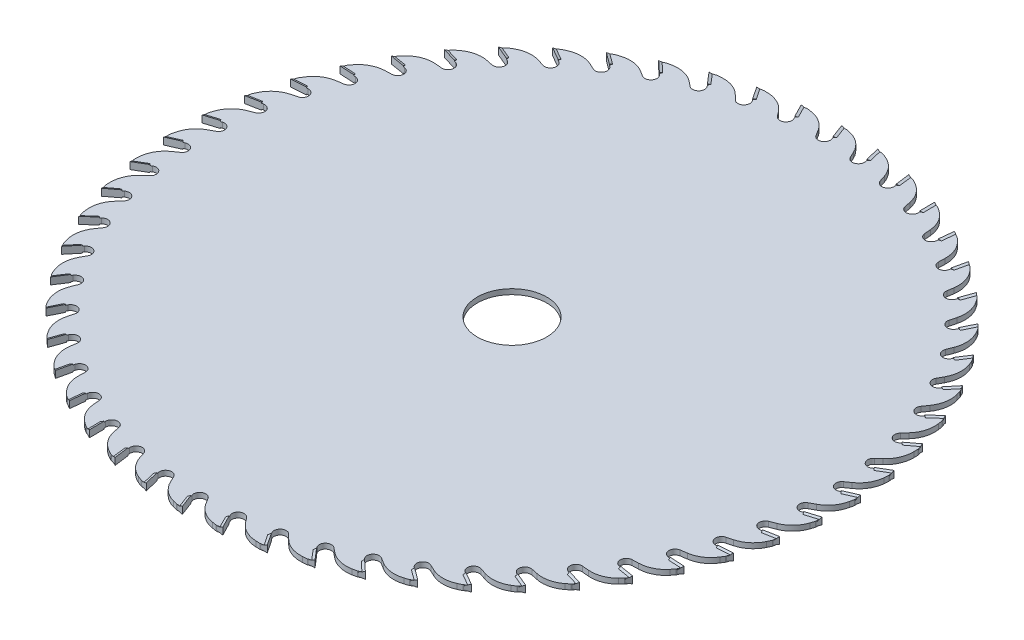
SolidWorks part; units mm, degrees
material "AISI Type A2 Tool Steel"
ref_plane "Front Plane" through (0, 0, 0) normal (0, 0, 1) x (1, 0, 0)
ref_plane "Top Plane" through (0, 0, 0) normal (0, 1, 0) x (1, 0, 0)
ref_plane "Right Plane" through (0, 0, 0) normal (1, 0, 0) x (0, 0, -1)
sketch "Sketch1" plane through (0, 0, 0) normal (0, 1, 0) x (1, 0, 0)
  line L0 (1.6393, 90.6125) -> (0, 95)
  line L1 (-1.4909, 89.0836) -> (-2.4449, 90.6357)
  line L2 (-8.0715, 94.3576) -> (-9.3059, 94.5431)
  line L3 (12.1477, 89.8095) -> (11.0288, 94.3576)
  line L4 (8.8612, 88.6543) -> (8.0938, 90.3067)
  line L5 (2.9373, 94.6567) -> (1.7328, 94.9842)
  line L6 (22.4918, 87.792) -> (21.9085, 92.4393)
  line L7 (19.0934, 87.0262) -> (18.523, 88.7564)
  line L8 (13.9064, 93.6756) -> (12.7481, 94.1408)
  line L9 (32.5317, 84.5872) -> (32.4919, 89.2708)
  line L10 (29.0674, 84.2211) -> (28.7018, 86.0059)
  line L11 (24.6874, 91.4278) -> (23.5909, 92.0243)
  line L12 (42.1318, 80.2386) -> (42.6359, 84.8951)
  line L13 (38.6484, 80.2771) -> (38.4924, 82.0923)
  line L14 (35.1346, 87.9436) -> (34.1148, 88.6633)
  line L15 (51.162, 74.8048) -> (52.2034, 79.3713)
  line L16 (47.7066, 75.2475) -> (47.7624, 77.0685)
  line L17 (45.1067, 83.27) -> (44.1773, 84.1033)
  line L18 (59.5004, 68.3595) -> (61.0648, 72.7742)
  line L19 (56.1198, 69.2003) -> (56.3866, 71.0025)
  line L20 (54.4687, 77.4704) -> (53.6424, 78.406)
  line L21 (67.0341, 60.9897) -> (69.1005, 65.193)
  line L22 (63.774, 62.2173) -> (64.2482, 63.9764)
  line L23 (63.0942, 70.6232) -> (62.382, 71.6483)
  line L24 (73.6613, 52.7951) -> (76.2017, 56.7301)
  line L25 (70.5657, 54.3929) -> (71.241, 56.085)
  line L26 (70.8664, 62.8208) -> (70.2781, 63.9217)
  line L27 (79.2924, 43.8866) -> (82.2724, 47.5)
  line L28 (76.4032, 45.8329) -> (77.2704, 47.4352)
  line L29 (77.6803, 54.169) -> (77.2238, 55.3307)
  line L30 (83.8512, 34.3845) -> (87.2305, 37.6276)
  line L31 (81.2075, 36.6532) -> (82.2548, 38.1439)
  line L32 (83.4437, 44.7846) -> (83.1251, 45.9915)
  line L33 (87.276, 24.4175) -> (91.009, 27.2463)
  line L34 (84.9136, 26.9777) -> (86.1268, 28.3368)
  line L35 (88.0787, 34.7945) -> (87.9023, 36.0303)
  line L36 (89.5206, 14.1203) -> (93.5567, 16.4966)
  line L37 (87.4713, 16.9374) -> (88.8342, 18.1465)
  line L38 (91.5225, 24.3339) -> (91.4908, 25.5818)
  line L39 (90.5545, 3.6321) -> (94.8393, 5.5238)
  line L40 (88.8462, 6.6681) -> (90.3402, 7.7108)
  line L41 (93.7287, 13.5443) -> (93.8421, 14.7874)
  line L42 (90.3639, -6.9052) -> (94.8393, -5.5238)
  line L43 (89.0196, -3.6914) -> (90.6245, -2.8292)
  line L44 (94.6673, 2.5715) -> (94.9242, 3.793)
  line L45 (88.9512, -17.3491) -> (93.5567, -16.4966)
  line L46 (87.9891, -14.001) -> (89.6833, -13.331)
  line L47 (94.3257, -8.4361) -> (94.7227, -7.2527)
  line L48 (86.3357, -27.5584) -> (91.009, -27.2463)
  line L49 (85.7687, -24.1212) -> (87.5293, -23.6524)
  line L50 (92.7086, -19.3296) -> (93.2403, -18.2003)
  line L51 (82.5526, -37.395) -> (87.2305, -37.6276)
  line L52 (82.3885, -33.9153) -> (84.1915, -33.654)
  line L53 (89.8377, -29.9617) -> (90.4969, -28.9018)
  line L54 (77.6531, -46.7259) -> (82.2724, -47.5)
  line L55 (77.8941, -43.2507) -> (79.7153, -43.2005)
  line L56 (85.7519, -40.1886) -> (86.5297, -39.2124)
  line L57 (71.7035, -55.425) -> (76.2017, -56.7301)
  line L58 (72.3463, -52.0012) -> (74.161, -52.1628)
  line L59 (80.5064, -49.8721) -> (81.3923, -48.9927)
  line L60 (64.7842, -63.3745) -> (69.1005, -65.193)
  line L61 (65.8202, -60.0485) -> (67.6038, -60.4196)
  line L62 (74.1723, -58.8811) -> (75.1543, -58.1105)
  line L63 (56.9888, -70.4669) -> (61.0648, -72.7742)
  line L64 (58.4039, -67.2837) -> (60.1324, -67.8594)
  line L65 (66.8351, -67.0938) -> (67.8999, -66.4425)
  line L66 (48.4228, -76.6065) -> (52.2034, -79.3713)
  line L67 (50.1978, -73.609) -> (51.8478, -74.3815)
  line L68 (58.594, -74.3993) -> (59.7273, -73.8759)
  line L69 (39.2019, -81.71) -> (42.6359, -84.8951)
  line L70 (41.3129, -78.9389) -> (42.8621, -79.8978)
  line L71 (49.5606, -80.6985) -> (50.747, -80.3103)
  line L72 (29.4509, -85.7086) -> (32.4919, -89.2708)
  line L73 (31.8693, -83.2013) -> (33.2967, -84.3335)
  line L74 (39.857, -85.9065) -> (41.0804, -85.6586)
  line L75 (19.3016, -88.5481) -> (21.9085, -92.4393)
  line L76 (21.9948, -86.3385) -> (23.281, -87.6288)
  line L77 (29.6143, -89.9528) -> (30.8582, -89.8486)
  line L78 (8.8912, -90.1901) -> (11.0288, -94.3576)
  line L79 (11.8228, -88.3082) -> (12.9505, -89.739)
  line L80 (18.9712, -92.7826) -> (20.2188, -92.8235)
  line L81 (-1.6393, -90.6125) -> (0, -95)
  line L82 (1.4909, -89.0836) -> (2.4449, -90.6357)
  line L83 (8.0715, -94.3576) -> (9.3059, -94.5431)
  line L84 (-12.1477, -89.8095) -> (-11.0288, -94.3576)
  line L85 (-8.8612, -88.6543) -> (-8.0938, -90.3067)
  line L86 (-2.9373, -94.6567) -> (-1.7328, -94.9842)
  line L87 (-22.4918, -87.792) -> (-21.9085, -92.4393)
  line L88 (-19.0934, -87.0262) -> (-18.523, -88.7564)
  line L89 (-13.9064, -93.6756) -> (-12.7481, -94.1408)
  line L90 (-32.5317, -84.5872) -> (-32.4919, -89.2708)
  line L91 (-29.0674, -84.2211) -> (-28.7018, -86.0059)
  line L92 (-24.6874, -91.4278) -> (-23.5909, -92.0243)
  line L93 (-42.1318, -80.2386) -> (-42.6359, -84.8951)
  line L94 (-38.6484, -80.2771) -> (-38.4924, -82.0923)
  line L95 (-35.1346, -87.9436) -> (-34.1148, -88.6633)
  line L96 (-51.162, -74.8048) -> (-52.2034, -79.3713)
  line L97 (-47.7066, -75.2475) -> (-47.7624, -77.0685)
  line L98 (-45.1067, -83.27) -> (-44.1773, -84.1033)
  line L99 (-59.5004, -68.3595) -> (-61.0648, -72.7742)
  line L100 (-56.1198, -69.2003) -> (-56.3866, -71.0025)
  line L101 (-54.4687, -77.4704) -> (-53.6424, -78.406)
  line L102 (-67.0341, -60.9897) -> (-69.1005, -65.193)
  line L103 (-63.774, -62.2173) -> (-64.2482, -63.9764)
  line L104 (-63.0942, -70.6232) -> (-62.382, -71.6483)
  line L105 (-73.6613, -52.7951) -> (-76.2017, -56.7301)
  line L106 (-70.5657, -54.3929) -> (-71.241, -56.085)
  line L107 (-70.8664, -62.8208) -> (-70.2781, -63.9217)
  line L108 (-79.2924, -43.8866) -> (-82.2724, -47.5)
  line L109 (-76.4032, -45.8329) -> (-77.2704, -47.4352)
  line L110 (-77.6803, -54.169) -> (-77.2238, -55.3307)
  line L111 (-83.8512, -34.3845) -> (-87.2305, -37.6276)
  line L112 (-81.2075, -36.6532) -> (-82.2548, -38.1439)
  line L113 (-83.4437, -44.7846) -> (-83.1251, -45.9915)
  line L114 (-87.276, -24.4175) -> (-91.009, -27.2463)
  line L115 (-84.9136, -26.9777) -> (-86.1268, -28.3368)
  line L116 (-88.0787, -34.7945) -> (-87.9023, -36.0303)
  line L117 (-89.5206, -14.1203) -> (-93.5567, -16.4966)
  line L118 (-87.4713, -16.9374) -> (-88.8342, -18.1465)
  line L119 (-91.5225, -24.3339) -> (-91.4908, -25.5818)
  line L120 (-90.5545, -3.6321) -> (-94.8393, -5.5238)
  line L121 (-88.8462, -6.6681) -> (-90.3402, -7.7108)
  line L122 (-93.7287, -13.5443) -> (-93.8421, -14.7874)
  line L123 (-90.3639, 6.9052) -> (-94.8393, 5.5238)
  line L124 (-89.0196, 3.6914) -> (-90.6245, 2.8292)
  line L125 (-94.6673, -2.5715) -> (-94.9242, -3.793)
  line L126 (-88.9512, 17.3491) -> (-93.5567, 16.4966)
  line L127 (-87.9891, 14.001) -> (-89.6833, 13.331)
  line L128 (-94.3257, 8.4361) -> (-94.7227, 7.2527)
  line L129 (-86.3357, 27.5584) -> (-91.009, 27.2463)
  line L130 (-85.7687, 24.1212) -> (-87.5293, 23.6524)
  line L131 (-92.7086, 19.3296) -> (-93.2403, 18.2003)
  line L132 (-82.5526, 37.395) -> (-87.2305, 37.6276)
  line L133 (-82.3885, 33.9153) -> (-84.1915, 33.654)
  line L134 (-89.8377, 29.9617) -> (-90.4969, 28.9018)
  line L135 (-77.6531, 46.7259) -> (-82.2724, 47.5)
  line L136 (-77.8941, 43.2507) -> (-79.7153, 43.2005)
  line L137 (-85.7519, 40.1886) -> (-86.5297, 39.2124)
  line L138 (-71.7035, 55.425) -> (-76.2017, 56.7301)
  line L139 (-72.3463, 52.0012) -> (-74.161, 52.1628)
  line L140 (-80.5064, 49.8721) -> (-81.3923, 48.9927)
  line L141 (-64.7842, 63.3745) -> (-69.1005, 65.193)
  line L142 (-65.8202, 60.0485) -> (-67.6038, 60.4196)
  line L143 (-74.1723, 58.8811) -> (-75.1543, 58.1105)
  line L144 (-56.9888, 70.4669) -> (-61.0648, 72.7742)
  line L145 (-58.4039, 67.2837) -> (-60.1324, 67.8594)
  line L146 (-66.8351, 67.0938) -> (-67.8999, 66.4425)
  line L147 (-48.4228, 76.6065) -> (-52.2034, 79.3713)
  line L148 (-50.1978, 73.609) -> (-51.8478, 74.3815)
  line L149 (-58.594, 74.3993) -> (-59.7273, 73.8759)
  line L150 (-39.2019, 81.71) -> (-42.6359, 84.8951)
  line L151 (-41.3129, 78.9389) -> (-42.8621, 79.8978)
  line L152 (-49.5606, 80.6985) -> (-50.747, 80.3103)
  line L153 (-29.4509, 85.7086) -> (-32.4919, 89.2708)
  line L154 (-31.8693, 83.2013) -> (-33.2967, 84.3335)
  line L155 (-39.857, 85.9065) -> (-41.0804, 85.6586)
  line L156 (-19.3016, 88.5481) -> (-21.9085, 92.4393)
  line L157 (-21.9948, 86.3385) -> (-23.281, 87.6288)
  line L158 (-29.6143, 89.9528) -> (-30.8582, 89.8486)
  line L159 (-8.8912, 90.1901) -> (-11.0288, 94.3576)
  line L160 (-11.8228, 88.3082) -> (-12.9505, 89.739)
  line L161 (-18.9712, 92.7826) -> (-20.2188, 92.8235)
  circle A0 centre (0, 0) radius 10
  circle A1 centre (0, 0) radius 95
  circle A2 centre (0, 90) radius 1.75
  arc A3 (-2.4449, 90.6357) -> (-8.0715, 94.3576) centre (-9.2603, 86.4464) ccw
  circle A4 centre (10.4484, 89.3915) radius 1.75
  arc A5 (8.0938, 90.3067) -> (2.9373, 94.6567) centre (0.8381, 86.937) ccw
  circle A6 centre (20.7554, 87.574) radius 1.75
  arc A7 (18.523, 88.7564) -> (13.9064, 93.6756) centre (10.9252, 86.2518) ccw
  circle A8 centre (30.7818, 84.5723) radius 1.75
  arc A9 (28.7018, 86.0059) -> (24.6874, 91.4278) centre (20.8645, 84.4003) ccw
  circle A10 centre (40.3919, 80.4269) radius 1.75
  arc A11 (38.4924, 82.0923) -> (35.1346, 87.9436) centre (30.5217, 81.4074) ccw
  circle A12 centre (49.4558, 75.1939) radius 1.75
  arc A13 (47.7624, 77.0685) -> (45.1067, 83.27) centre (39.7662, 77.3136) ccw
  circle A14 centre (57.8509, 68.944) radius 1.75
  arc A15 (56.3866, 71.0025) -> (54.4687, 77.4704) centre (48.4729, 72.1742) ccw
  circle A16 centre (65.4636, 61.7617) radius 1.75
  arc A17 (64.2482, 63.9764) -> (63.0942, 70.6232) centre (56.524, 66.0589) ccw
  circle A18 centre (72.1911, 53.7443) radius 1.75
  arc A19 (71.241, 56.085) -> (70.8664, 62.8208) centre (63.8108, 59.0502) ccw
  circle A20 centre (77.9423, 45) radius 1.75
  arc A21 (77.2704, 47.4352) -> (77.6803, 54.169) centre (70.2346, 51.2429) ccw
  circle A22 centre (82.6394, 35.6472) radius 1.75
  arc A23 (82.2548, 38.1439) -> (83.4437, 44.7846) centre (75.7087, 42.7427) ccw
  circle A24 centre (86.2191, 25.8123) radius 1.75
  arc A25 (86.1268, 28.3368) -> (88.0787, 34.7945) centre (80.1589, 33.6644) ccw
  circle A26 centre (88.6327, 15.6283) radius 1.75
  arc A27 (88.8342, 18.1465) -> (91.5225, 24.3339) centre (83.5251, 24.1309) ccw
  circle A28 centre (89.8477, 5.233) radius 1.75
  arc A29 (90.3402, 7.7108) -> (93.7287, 13.5443) centre (85.7617, 14.2711) ccw
  circle A30 centre (89.8477, -5.233) radius 1.75
  arc A31 (90.6245, -2.8292) -> (94.6673, 2.5715) centre (86.8386, 4.2183) ccw
  circle A32 centre (88.6327, -15.6283) radius 1.75
  arc A33 (89.6833, -13.331) -> (94.3257, -8.4361) centre (86.7412, -5.8916) ccw
  circle A34 centre (86.2191, -25.8123) radius 1.75
  arc A35 (87.5293, -23.6524) -> (92.7086, -19.3296) centre (85.4707, -15.9218) ccw
  circle A36 centre (82.6394, -35.6472) radius 1.75
  arc A37 (84.1915, -33.654) -> (89.8377, -29.9617) centre (83.0443, -25.7367) ccw
  circle A38 centre (77.9423, -45) radius 1.75
  arc A39 (79.7153, -43.2005) -> (85.7519, -40.1886) centre (79.495, -35.2035) ccw
  circle A40 centre (72.1911, -53.7443) radius 1.75
  arc A41 (74.161, -52.1628) -> (80.5064, -49.8721) centre (74.8706, -44.1943) ccw
  circle A42 centre (65.4636, -61.7617) radius 1.75
  arc A43 (67.6038, -60.4196) -> (74.1723, -58.8811) centre (69.2337, -52.5874) ccw
  circle A44 centre (57.8509, -68.944) radius 1.75
  arc A45 (60.1324, -67.8594) -> (66.8351, -67.0938) centre (62.6605, -60.2694) ccw
  circle A46 centre (49.4558, -75.1939) radius 1.75
  arc A47 (51.8478, -74.3815) -> (58.594, -74.3993) centre (55.24, -67.1363) ccw
  circle A48 centre (40.3919, -80.4269) radius 1.75
  arc A49 (42.8621, -79.8978) -> (49.5606, -80.6985) centre (47.0724, -73.0953) ccw
  circle A50 centre (30.7818, -84.5723) radius 1.75
  arc A51 (33.2967, -84.3335) -> (39.857, -85.9065) centre (38.2683, -78.0659) ccw
  circle A52 centre (20.7554, -87.574) radius 1.75
  arc A53 (23.281, -87.6288) -> (29.6143, -89.9528) centre (28.9467, -81.9807) ccw
  circle A54 centre (10.4484, -89.3915) radius 1.75
  arc A55 (12.9505, -89.739) -> (18.9712, -92.7826) centre (19.2335, -84.7869) ccw
  circle A56 centre (0, -90) radius 1.75
  arc A57 (2.4449, -90.6357) -> (8.0715, -94.3576) centre (9.2603, -86.4464) ccw
  circle A58 centre (-10.4484, -89.3915) radius 1.75
  arc A59 (-8.0938, -90.3067) -> (-2.9373, -94.6567) centre (-0.8381, -86.937) ccw
  circle A60 centre (-20.7554, -87.574) radius 1.75
  arc A61 (-18.523, -88.7564) -> (-13.9064, -93.6756) centre (-10.9252, -86.2518) ccw
  circle A62 centre (-30.7818, -84.5723) radius 1.75
  arc A63 (-28.7018, -86.0059) -> (-24.6874, -91.4278) centre (-20.8645, -84.4003) ccw
  circle A64 centre (-40.3919, -80.4269) radius 1.75
  arc A65 (-38.4924, -82.0923) -> (-35.1346, -87.9436) centre (-30.5217, -81.4074) ccw
  circle A66 centre (-49.4558, -75.1939) radius 1.75
  arc A67 (-47.7624, -77.0685) -> (-45.1067, -83.27) centre (-39.7662, -77.3136) ccw
  circle A68 centre (-57.8509, -68.944) radius 1.75
  arc A69 (-56.3866, -71.0025) -> (-54.4687, -77.4704) centre (-48.4729, -72.1742) ccw
  circle A70 centre (-65.4636, -61.7617) radius 1.75
  arc A71 (-64.2482, -63.9764) -> (-63.0942, -70.6232) centre (-56.524, -66.0589) ccw
  circle A72 centre (-72.1911, -53.7443) radius 1.75
  arc A73 (-71.241, -56.085) -> (-70.8664, -62.8208) centre (-63.8108, -59.0502) ccw
  circle A74 centre (-77.9423, -45) radius 1.75
  arc A75 (-77.2704, -47.4352) -> (-77.6803, -54.169) centre (-70.2346, -51.2429) ccw
  circle A76 centre (-82.6394, -35.6472) radius 1.75
  arc A77 (-82.2548, -38.1439) -> (-83.4437, -44.7846) centre (-75.7087, -42.7427) ccw
  circle A78 centre (-86.2191, -25.8123) radius 1.75
  arc A79 (-86.1268, -28.3368) -> (-88.0787, -34.7945) centre (-80.1589, -33.6644) ccw
  circle A80 centre (-88.6327, -15.6283) radius 1.75
  arc A81 (-88.8342, -18.1465) -> (-91.5225, -24.3339) centre (-83.5251, -24.1309) ccw
  circle A82 centre (-89.8477, -5.233) radius 1.75
  arc A83 (-90.3402, -7.7108) -> (-93.7287, -13.5443) centre (-85.7617, -14.2711) ccw
  circle A84 centre (-89.8477, 5.233) radius 1.75
  arc A85 (-90.6245, 2.8292) -> (-94.6673, -2.5715) centre (-86.8386, -4.2183) ccw
  circle A86 centre (-88.6327, 15.6283) radius 1.75
  arc A87 (-89.6833, 13.331) -> (-94.3257, 8.4361) centre (-86.7412, 5.8916) ccw
  circle A88 centre (-86.2191, 25.8123) radius 1.75
  arc A89 (-87.5293, 23.6524) -> (-92.7086, 19.3296) centre (-85.4707, 15.9218) ccw
  circle A90 centre (-82.6394, 35.6472) radius 1.75
  arc A91 (-84.1915, 33.654) -> (-89.8377, 29.9617) centre (-83.0443, 25.7367) ccw
  circle A92 centre (-77.9423, 45) radius 1.75
  arc A93 (-79.7153, 43.2005) -> (-85.7519, 40.1886) centre (-79.495, 35.2035) ccw
  circle A94 centre (-72.1911, 53.7443) radius 1.75
  arc A95 (-74.161, 52.1628) -> (-80.5064, 49.8721) centre (-74.8706, 44.1943) ccw
  circle A96 centre (-65.4636, 61.7617) radius 1.75
  arc A97 (-67.6038, 60.4196) -> (-74.1723, 58.8811) centre (-69.2337, 52.5874) ccw
  circle A98 centre (-57.8509, 68.944) radius 1.75
  arc A99 (-60.1324, 67.8594) -> (-66.8351, 67.0938) centre (-62.6605, 60.2694) ccw
  circle A100 centre (-49.4558, 75.1939) radius 1.75
  arc A101 (-51.8478, 74.3815) -> (-58.594, 74.3993) centre (-55.24, 67.1363) ccw
  circle A102 centre (-40.3919, 80.4269) radius 1.75
  arc A103 (-42.8621, 79.8978) -> (-49.5606, 80.6985) centre (-47.0724, 73.0953) ccw
  circle A104 centre (-30.7818, 84.5723) radius 1.75
  arc A105 (-33.2967, 84.3335) -> (-39.857, 85.9065) centre (-38.2683, 78.0659) ccw
  circle A106 centre (-20.7554, 87.574) radius 1.75
  arc A107 (-23.281, 87.6288) -> (-29.6143, 89.9528) centre (-28.9467, 81.9807) ccw
  circle A108 centre (-10.4484, 89.3915) radius 1.75
  arc A109 (-12.9505, 89.739) -> (-18.9712, 92.7826) centre (-19.2335, 84.7869) ccw
  dimension "D1" = 190
  dimension "D2" = 20
  dimension "D3" = 3.5
  dimension "D5" = 8
  dimension "D4" = 5
  dimension "D6" = 54
extrude "Boss-Extrude1" add sketch "Sketch1" along normal mid plane 1.5 contours L160 A109 L161 A1 L156 A106 L157 A107 L158 L153 A104 L154 A105 L155 L150 A102 L151 A103 L152 L147 A100 L148 A101 L149 L144 A98 L145 A99 L146 L141 A96 L142 A97 L143 L138 A94 L139 A95 L140 L135 A92 L136 A93 L137 region at (3.3357, 0, -93.7463)
sketch "Sketch2" plane through (-31.1469, 0, 11.6375) normal (0.9367, 0, -0.35) x (-0.35, 0, -0.9367)
  line L0 (-88.9912, 0.75) -> (-88.9912, -0.75) construction
  line L1 (-88.9912, 1) -> (-84.768, 1)
  line L2 (-88.9912, 1) -> (-88.9912, -1)
  line L3 (-88.9912, -1) -> (-84.768, -1)
  line L4 (-84.768, 1) -> (-84.768, -1)
  line L5 (104.4402, 0) -> (-104.4402, 0) construction
  point P6 (-88.9912, 0)
  dimension "D1" = 2
extrude "Boss-Extrude2" add sketch "Sketch2" against normal blind 1.5 draft 20
pattern_circular "CirPattern1" count 54 over 360 about axis through (0, 0.75, 0) along (0, 1, 0) of "Boss-Extrude2"
equation "\"Inner diameter\"= \"D2@Sketch1\""
